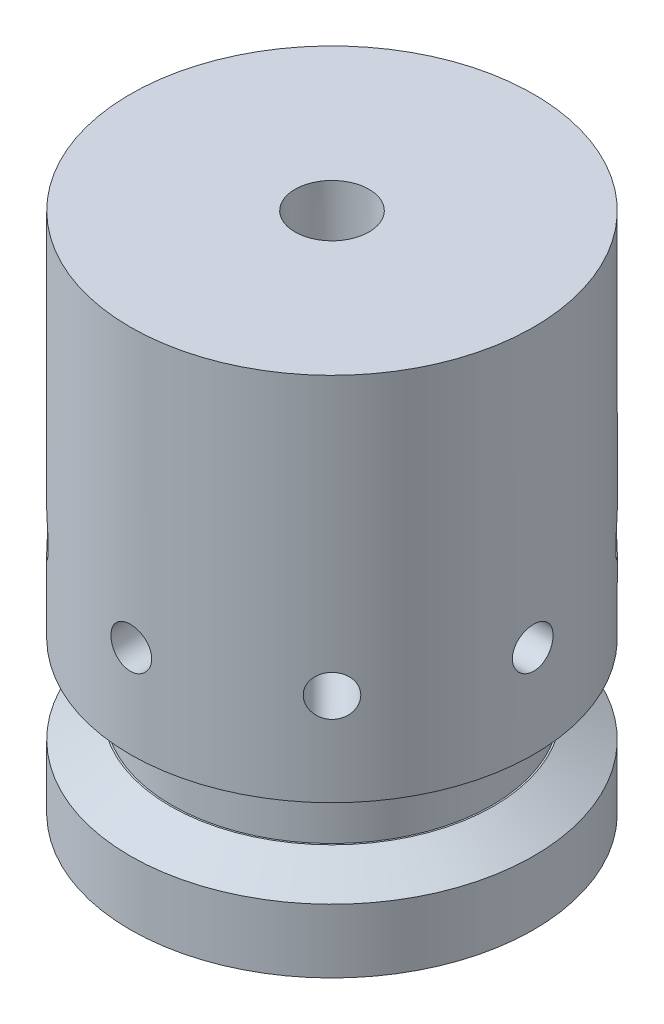
SolidWorks part; units mm, degrees
ref_plane "Front" through (0, 0, 0) normal (0, 0, 1) x (1, 0, 0)
ref_plane "Top" through (0, 0, 0) normal (0, 1, 0) x (1, 0, 0)
ref_plane "Right" through (0, 0, 0) normal (1, 0, 0) x (0, 0, -1)
sketch "Sketch2" plane through (0, 0, 0) normal (0, 0, 1) x (1, 0, 0)
  line L0 (0, 19.1415) -> (0, -24.752) construction
  line L1 (-15.8413, 0) -> (18.4815, 0) construction
  line L2 (-15.8413, 4) -> (18.4815, 4) construction
  line L3 (-1.7, 0) -> (-1.7, 4)
  line L4 (-10.9, 21.0703) -> (-10.9, -1) construction
  line L5 (-1.7, 0) -> (-10.9, -9.2)
  line L6 (-10.9, -9.2) -> (-10.9, -4.5)
  line L7 (-18.3668, 19) -> (19.9717, 19) construction
  line L8 (-1.7, 4) -> (-2, 19)
  line L9 (-2, 19) -> (-10.9, 19)
  line L10 (-10.9, 19) -> (-10.9, 4)
  line L11 (-10.9, -1) -> (-10.9, 4)
  line L12 (-10.9, -1) -> (-8.65, -1)
  line L14 (-10.9, -4.5) -> (-8.65, -4.5)
  line L15 (-8.65, -1) -> (-8.65, -4.5)
  line L16 (-10.9, -4.5) -> (-10.9, -24.752) construction
  dimension "D1" = 10.9
  dimension "D2" = 4
  dimension "D3" = 45
  dimension "D4" = 15
  dimension "D5" = 3.5
  dimension "ThrottleRadius" = 1.7
  dimension "NozzleRadius" = 2
  dimension "D6" = 2.25
  dimension "D7" = 1
revolve "Revolve1" add sketch "Sketch2" angle 360 about L0
ref_plane "Plane1" through (-10.9, 0, 0) normal (-1, 0, 0) x (0, 0, 1)
sketch "Sketch3" plane through (-10.9, 0, 0) normal (-1, 0, 0) x (0, 0, 1)
  line L0 (0, 19) -> (0, -8.4987) construction
  line L1 (2, 19) -> (-2, 19) construction
  line L2 (10.9, 19) -> (-10.9, 19) construction
  circle A0 centre (0, 4) radius 1.1
  dimension "D1" = 2.2
  dimension "D2" = 15
extrude "Cut-Extrude1" cut sketch "Sketch3" against normal blind 7
ref_axis "Axis1" through (0, 0, 0) along (0, 1, 0)
pattern_circular "CirPattern1" count 8 over 360 about axis through (0, 0, 0) along (0, 1, 0) of "Cut-Extrude1"
chamfer "Chamfer2" distance 1.25 angle 60 1 edges at (0, -4.5, 10.9) first distance on face at (0, -9.2, 10.9)
ref_plane "Plane2" through (0, 0, 0) normal (0, -1, 0) x (-1, 0, 0)
sketch "Sketch4" plane through (0, 0, 0) normal (0, -1, 0) x (-1, 0, 0)
  line L1 (3.9837, 0) -> (1.9919, 3.45)
  line L2 (1.9919, 3.45) -> (-1.9919, 3.45)
  line L3 (-1.9919, 3.45) -> (-3.9837, 0)
  line L4 (-3.9837, 0) -> (-1.9919, -3.45)
  line L5 (-1.9919, -3.45) -> (1.9919, -3.45)
  line L6 (1.9919, -3.45) -> (3.9837, 0)
  circle A0 centre (0, 0) radius 3.45 construction
  dimension "D1" = 6.9
extrude "Cut-Extrude2" cut sketch "Sketch4" against normal blind 1 and the other way blind 3
fillet "Fillet1" radius 0.5 6 edges at (2.8627, -1.7591, 1.9416) (-0.108, -1.7517, 3.45) (-3.1129, -1.7591, 1.5084) (-2.8627, -1.7591, -1.9416) (-0.108, -1.7517, -3.45) (3.1129, -1.7591, -1.5084)
